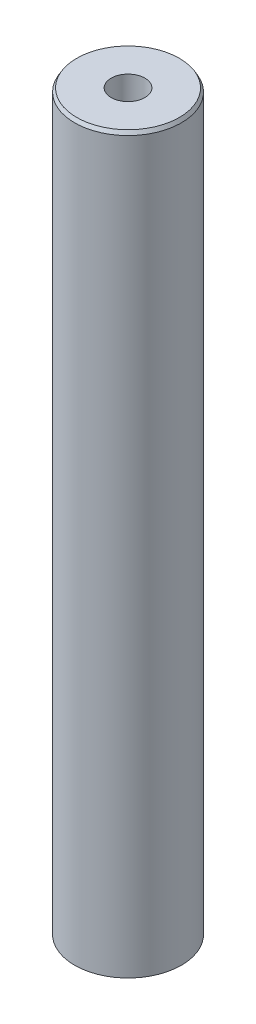
SolidWorks part; units mm, degrees
ref_plane "Front Plane" through (0, 0, 0) normal (0, 0, 1) x (1, 0, 0)
ref_plane "Top Plane" through (0, 0, 0) normal (0, 1, 0) x (1, 0, 0)
ref_plane "Right Plane" through (0, 0, 0) normal (1, 0, 0) x (0, 0, -1)
sketch "Sketch1" plane through (0, 0, 0) normal (0, 1, 0) x (1, 0, 0)
  circle A0 centre (0, 0) radius 40
  dimension "SHAFT_OD" = 80
extrude "Boss-Extrude1" add sketch "Sketch1" along normal blind 550.8727
sketch "Sketch2" plane through (0, 0, 0) normal (0, 1, 0) x (1, 0, 0)
  circle A0 centre (0, 0) radius 12.6492
  dimension "BORE_D" = 25.2984
extrude "Cut-Extrude1" cut sketch "Sketch2" along normal through all
chamfer "Chamfer1" distance 2.7047 angle 30 2 edges at (0, 550.8727, 40) (0, 0, 40) first distance on face at (0, 550.8727, 40) first distance on face at (0, 0, 12.6492)
